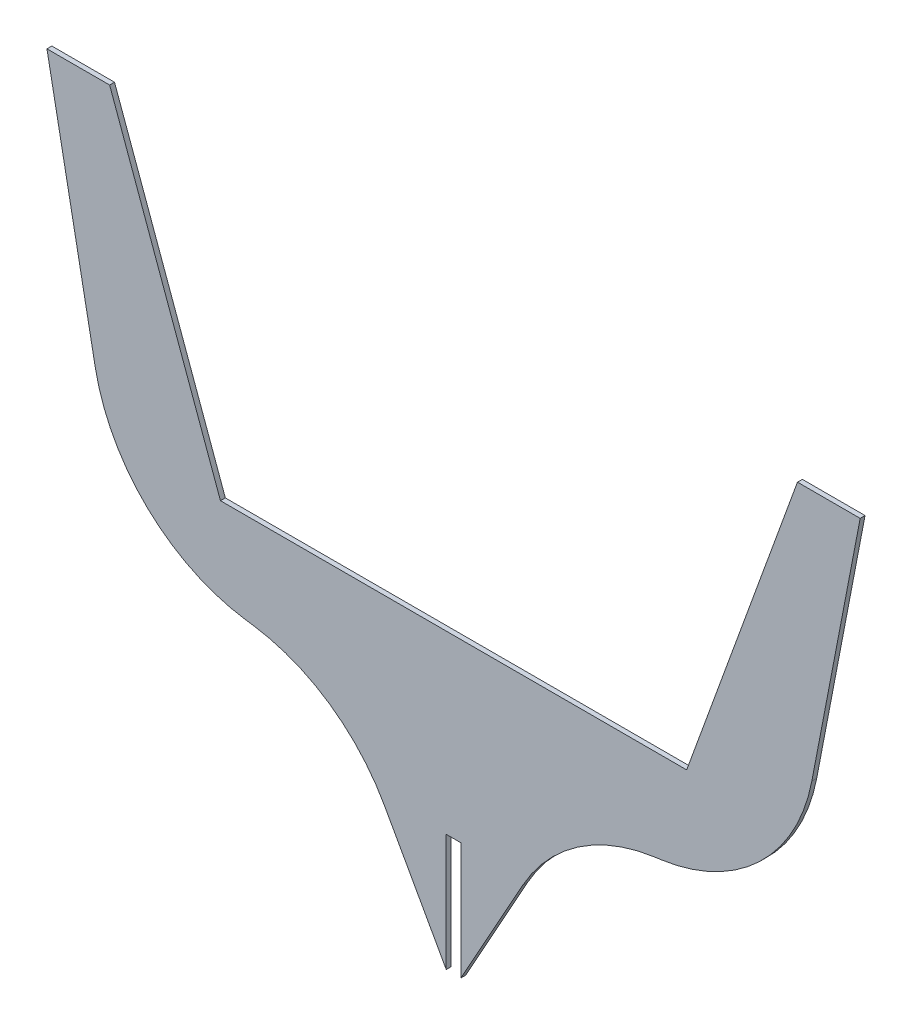
SolidWorks part; units mm, degrees
ref_plane "Plan de face" through (0, 0, 0) normal (0, 0, 1) x (1, 0, 0)
ref_plane "Plan de dessus" through (0, 0, 0) normal (0, 1, 0) x (1, 0, 0)
ref_plane "Plan de droite" through (0, 0, 0) normal (1, 0, 0) x (0, 0, -1)
sketch "Esquisse3" plane through (0, 0, 0) normal (0, 0, 1) x (1, 0, 0)
  line L46 (-5.9932, 123.5769) -> (62.1298, -63.698)
  line L48 (-44.5416, 123.5769) -> (0, -108.3483)
  line L49 (0, -108.3483) -> (136.3361, -127.6909)
  line L50 (136.3361, -127.6909) -> (200.9584, -243.9231)
  line L51 (200.9584, -243.9231) -> (200.9584, -171.9231)
  line L54 (205.4584, -171.9231) -> (205.4584, 18.2487) construction
  line L67 (-44.5416, 123.5769) -> (-5.9932, 123.5769)
  line L68 (62.1298, -63.698) -> (348.7871, -63.698)
  line L69 (200.9584, -171.9231) -> (209.9584, -171.9231)
  line L70 (455.4584, 123.5769) -> (416.91, 123.5769)
  line L71 (209.9584, -243.9231) -> (209.9584, -171.9231)
  line L72 (274.5808, -127.6909) -> (209.9584, -243.9231)
  line L73 (410.9169, -108.3483) -> (274.5808, -127.6909)
  line L74 (455.4584, 123.5769) -> (410.9169, -108.3483)
  line L75 (416.91, 123.5769) -> (348.7871, -63.698)
  point P6 (205.4584, -63.698)
  point P16 (57.9997, 63.6572)
  point P17 (-21.8235, -154.8228)
  point P18 (56.6782, -128.6556)
  point P19 (0, -114.4816)
  point P20 (62.1298, -101.398)
  point P21 (300.6175, -198.9217)
  point P23 (136.3361, -165.1909)
  point P24 (0, -108.3483)
  dimension "D1" = 500
  dimension "D2" = 9
  dimension "D3" = 295.5
  dimension "D4" = 72
  dimension "D5" = 108.2251
extrude "Boss.-Extru.3" add sketch "Esquisse3" along normal blind 3
fillet "Congé1" radius 110 4 edges at (410.9169, -108.3483, 1.5) (274.5808, -127.6909, 1.5) (136.3361, -127.6909, 1.5) (0, -108.3483, 1.5)
